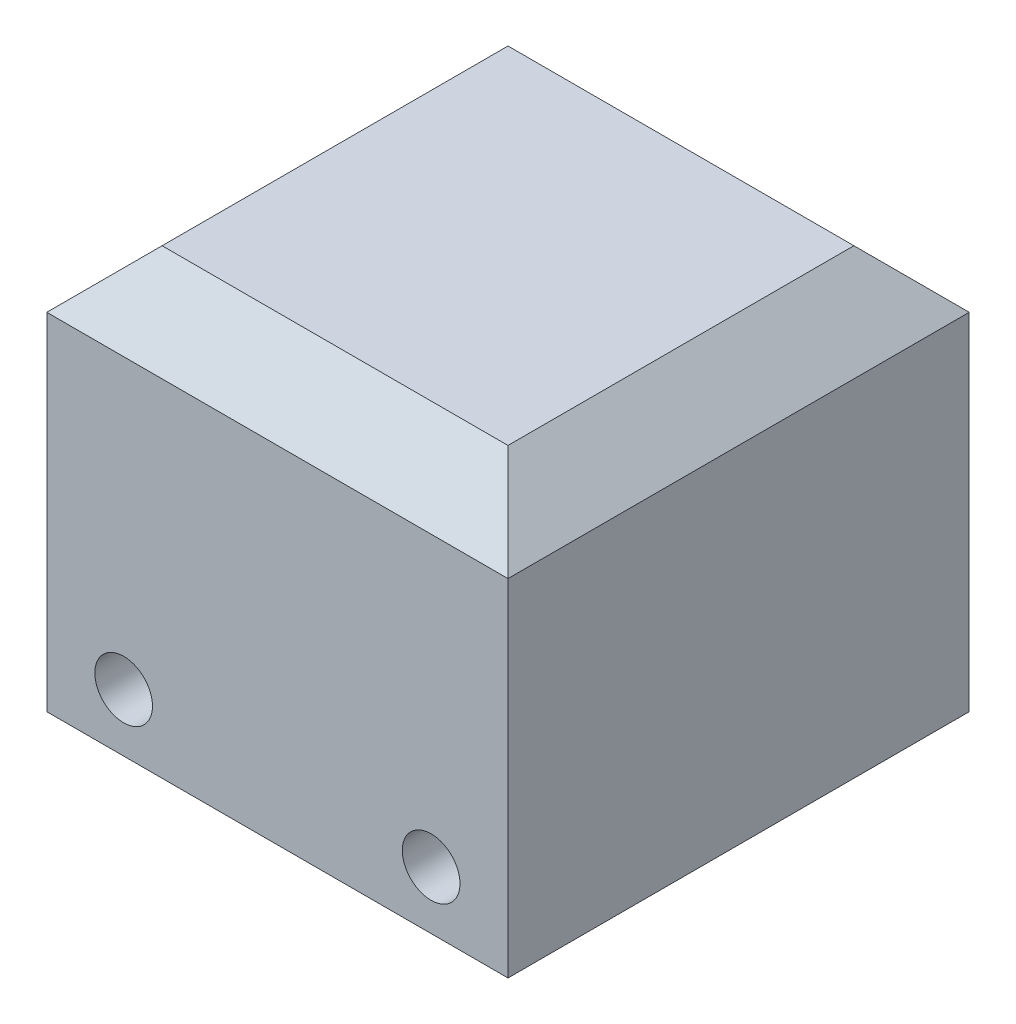
SolidWorks part; units mm, degrees
ref_plane "Front Plane" through (0, 0, 0) normal (0, 0, 1) x (1, 0, 0)
ref_plane "Top Plane" through (0, 0, 0) normal (0, 1, 0) x (1, 0, 0)
ref_plane "Right Plane" through (0, 0, 0) normal (1, 0, 0) x (0, 0, -1)
sketch "Sketch1" plane through (0, 0, 0) normal (0, 0, 1) x (1, 0, 0)
  line L0 (-6.35, 21.7518) -> (-6.35, -54.4482) construction
  line L1 (-44.45, 21.7518) -> (31.75, 21.7518)
  line L2 (-44.45, 21.7518) -> (-44.45, -54.4482)
  line L3 (-44.45, -54.4482) -> (31.75, -54.4482)
  line L4 (31.75, 21.7518) -> (31.75, -54.4482)
  line L5 (-44.45, 21.7518) -> (31.75, -54.4482) construction
  line L6 (-44.45, -54.4482) -> (31.75, 21.7518) construction
  circle A0 centre (-31.75, -35.3982) radius 4.7625
  circle A1 centre (19.05, -35.3982) radius 4.7625
  point P0 (-6.35, -16.3482)
  dimension "D4" = 9.525
  dimension "D1" = 76.2
  dimension "D2" = 19.05
  dimension "D3" = 12.7
extrude "Boss-Extrude1" add sketch "Sketch1" along normal blind 38.1 and the other way blind 38.1
chamfer "Chamfer1" distance 9.525 angle 45 8 edges at (-6.35, -54.4482, -38.1) (-44.45, -54.4482, 0) (-6.35, -54.4482, 38.1) (31.75, -54.4482, 0) (-6.35, 21.7518, -38.1) (31.75, 21.7518, 0) (-6.35, 21.7518, 38.1) (-44.45, 21.7518, 0)
ref_plane "Plane1" through (-3.175, 0, 3.175) normal (-0.7071, 0, 0.7071) x (0.7071, 0, 0.7071)
